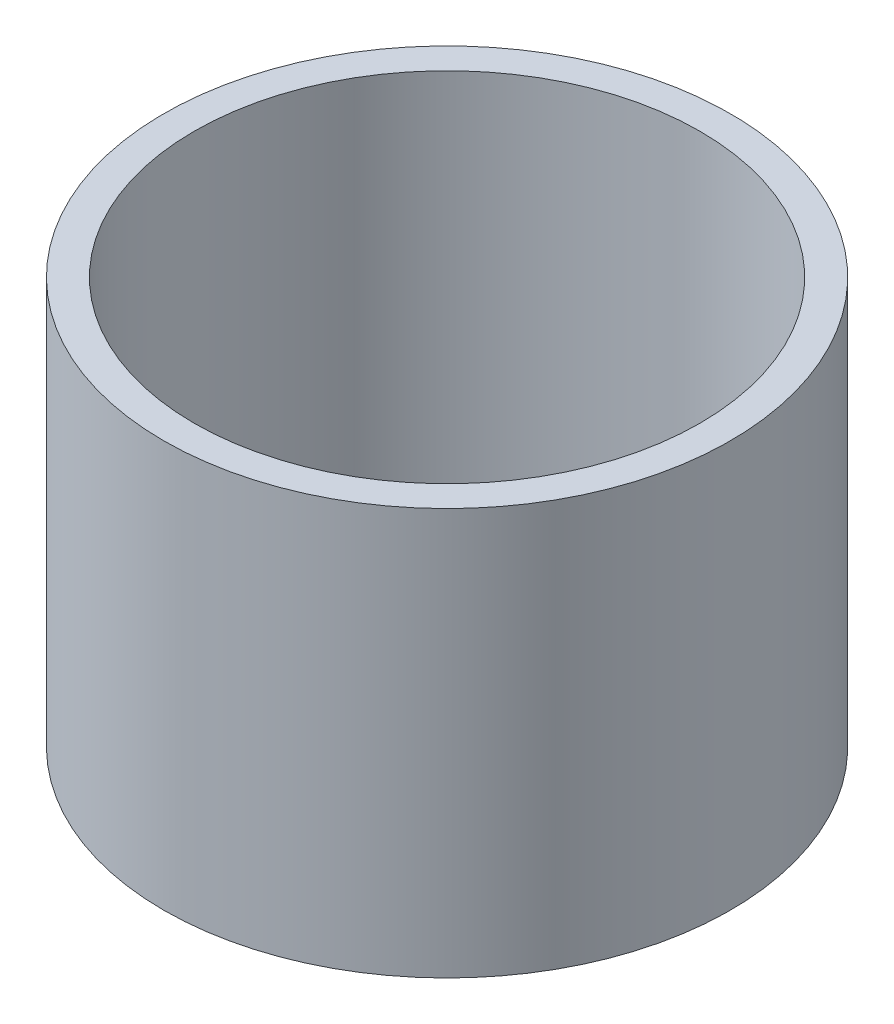
SolidWorks part; units mm, degrees
ref_plane "Front Plane" through (0, 0, 0) normal (0, 0, 1) x (1, 0, 0)
ref_plane "Top Plane" through (0, 0, 0) normal (0, 1, 0) x (1, 0, 0)
ref_plane "Right Plane" through (0, 0, 0) normal (1, 0, 0) x (0, 0, -1)
sketch "Sketch1" plane through (0, 0, 0) normal (0, 1, 0) x (1, 0, 0)
  circle A0 centre (0, 0) radius 42.5
  dimension "SLEEVE_OD" = 85
extrude "Boss-Extrude1" add sketch "Sketch1" along normal blind 60.9873
sketch "Sketch2" plane through (0, 0, 0) normal (0, 1, 0) x (1, 0, 0)
  circle A0 centre (0, 0) radius 37.9392
  dimension "BORE_D" = 75.8785
extrude "Cut-Extrude1" cut sketch "Sketch2" along normal through all
chamfer "Chamfer1" distance 3.5963 angle 60 rebuild error yes
